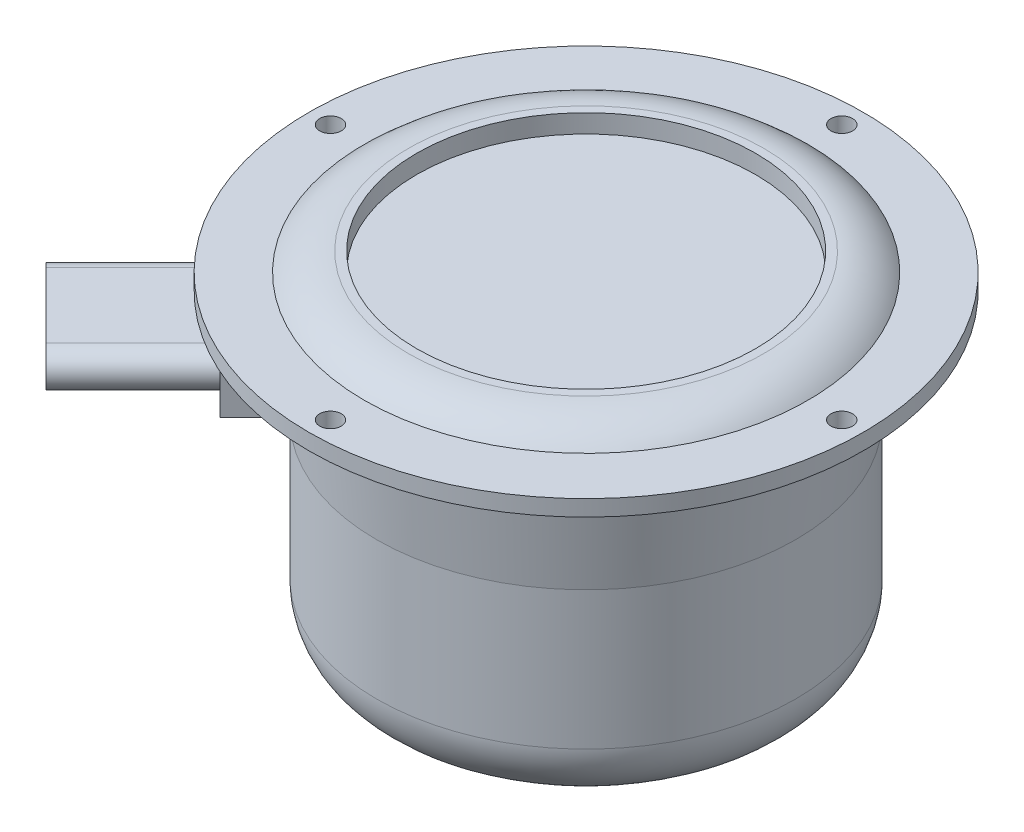
SolidWorks part; units mm, degrees
ref_plane "前视基准面" through (0, 0, 0) normal (0, 0, 1) x (1, 0, 0)
ref_plane "上视基准面" through (0, 0, 0) normal (0, 1, 0) x (1, 0, 0)
ref_plane "右视基准面" through (0, 0, 0) normal (1, 0, 0) x (0, 0, -1)
other "Configuration Table"
sketch "草图1" plane through (0, 0, 0) normal (0, 1, 0) x (1, 0, 0)
  line L0 (-1000, 0) -> (49000, 0) construction
  line L1 (0, -1000) -> (0, 49000) construction
  circle A0 centre (0, 0) radius 45
  circle A1 centre (0, 0) radius 41.5 construction
  circle A2 centre (41.5, 0) radius 1.75
  circle A3 centre (-41.5, 0) radius 1.75
  circle A4 centre (0, 41.5) radius 1.75
  circle A5 centre (0, -41.5) radius 1.75
  point P8 (45, 0)
  dimension "D1" = 90
  dimension "D2" = 83
  dimension "D3" = 3.5
  dimension "D5" = 3.5
  dimension "D6" = 3.5
  dimension "D7" = 3.5
  dimension "D4" = 3.5
extrude "凸台-拉伸1" add sketch "草图1" along normal blind 2.6
sketch "草图2" plane through (0, 0, 0) normal (0, -1, 0) x (1, 0, 0)
  circle A0 centre (0, 0) radius 35.5
  dimension "D1" = 71
ref_plane "基准面1" through (0, -18, 0) normal (0, -1, 0) x (-1, 0, 0)
sketch "草图3" plane through (0, -18, 0) normal (0, -1, 0) x (-1, 0, 0)
  circle A0 centre (0, 0) radius 34
  dimension "D1" = 68
loft "放样1" add profiles "草图3", "草图2" connector at (30.174, -18, -15.6694) connector at (31.8702, 0, -15.6379)
sketch "草图4" plane through (0, -18, 0) normal (0, -1, 0) x (1, 0, 0)
  circle A1 centre (0, 0) radius 34
  circle A2 centre (0, 0) radius 34
  dimension "D1" = 0
extrude "凸台-拉伸2" add sketch "草图4" along normal blind 32.4
fillet "圆角1" radius 10 1 edges at (0, -50.4, -34)
sketch "草图5" plane through (0, 0, 0) normal (0, -1, 0) x (1, 0, 0)
  line L0 (-1000, 0) -> (49000, 0) construction
  line L1 (0, 0) -> (-35355.3391, 35355.3391) construction
  line L2 (-17.6777, 33.234) -> (-33.234, 17.6777)
  line L3 (-21.9203, 37.4767) -> (-37.4767, 21.9203)
  line L4 (-21.9203, 37.4767) -> (-17.6777, 33.234)
  line L5 (-37.4767, 21.9203) -> (-33.234, 17.6777)
  dimension "D1" = 45
  dimension "D2" = 36
  dimension "D3" = 11
  dimension "D4" = 11
  dimension "D5" = 6
extrude "凸台-拉伸3" add sketch "草图5" along normal blind 10
sketch "草图6" plane through (-29.6985, 0, 29.6985) normal (-0.7071, 0, 0.7071) x (0.7071, 0, 0.7071)
  line L0 (0, -1010) -> (0, 48990) construction
  line L1 (11, -10) -> (-11, -10) construction
  line L2 (-7.5, -5) -> (7.5, -5) construction
  line L3 (-7.5, -2) -> (7.5, -2)
  line L4 (-7.5, -8) -> (7.5, -8)
  line L5 (11, 0) -> (-11, 0) construction
  arc A0 (-7.5, -2) -> (-7.5, -8) centre (-7.5, -5) ccw
  arc A1 (7.5, -8) -> (7.5, -2) centre (7.5, -5) ccw
  point P5 (0, -10)
  point P7 (0, -5)
  dimension "D3" = 3
  dimension "D1" = 15
  dimension "D2" = 5
extrude "凸台-拉伸4" add sketch "草图6" along normal blind 20
sketch "草图7" plane through (0, 2.6, 0) normal (0, 1, 0) x (1, 0, 0)
  circle A0 centre (0, 0) radius 27.5
  circle A1 centre (0, 0) radius 36
  dimension "D1" = 55
  dimension "D2" = 8.5
extrude "凸台-拉伸5" add sketch "草图7" along normal blind 3
fillet "圆角2" radius 10 1 edges at (0, 5.6, 36)
